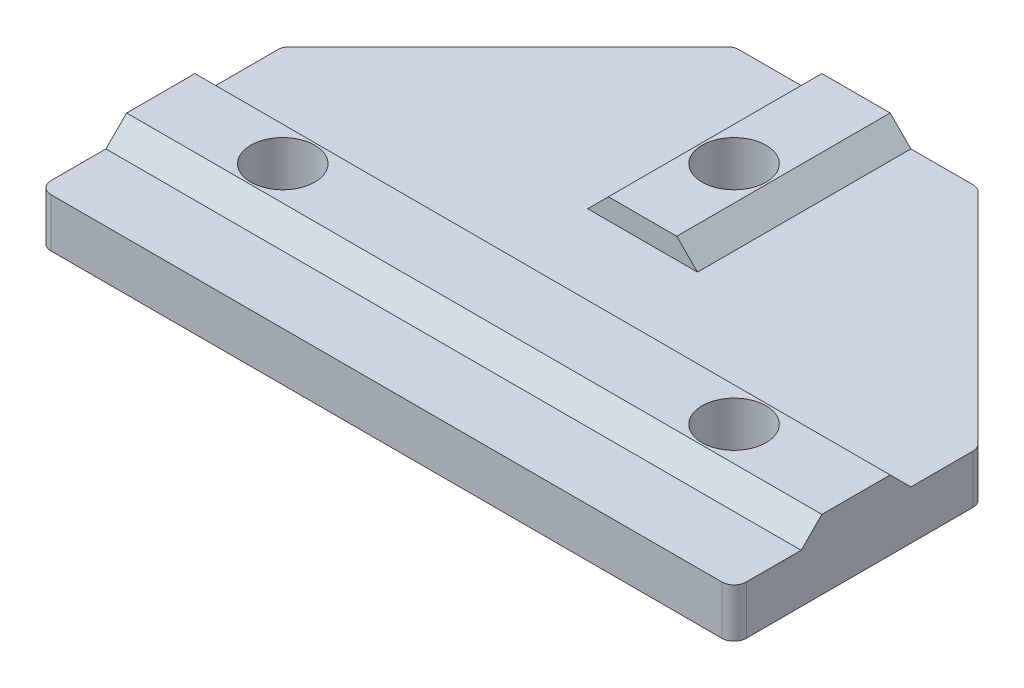
SolidWorks part; units mm, degrees
ref_plane "Front Plane" through (0, 0, 0) normal (0, 0, 1) x (1, 0, 0)
ref_plane "Top Plane" through (0, 0, 0) normal (0, 1, 0) x (1, 0, 0)
ref_plane "Right Plane" through (0, 0, 0) normal (1, 0, 0) x (0, 0, -1)
sketch "Sketch1" plane through (0, 0, 0) normal (0, 1, 0) x (1, 0, 0)
  line L0 (0, 0) -> (57, 0)
  line L1 (57, 0) -> (57, 20)
  line L2 (57, 20) -> (38.5, 38.5)
  line L3 (38.5, 38.5) -> (18.5, 38.5)
  line L4 (18.5, 38.5) -> (0, 20)
  line L5 (0, 20) -> (0, 0)
  dimension "D1" = 135
  dimension "D2" = 135
  dimension "D3" = 57
  dimension "D4" = 38.5
  dimension "D5" = 20
extrude "Boss-Extrude1" add sketch "Sketch1" along normal blind 4
sketch "Sketch2" plane through (0, 4, 0) normal (0, 1, 0) x (1, 0, 0)
  line L0 (38.5, 38.5) -> (18.5, 38.5) construction
  line L1 (33, 38.5) -> (24, 38.5)
  line L2 (33, 38.5) -> (33, 21)
  line L3 (33, 21) -> (24, 21)
  line L4 (24, 38.5) -> (24, 21)
  line L5 (0, 20) -> (0, 0) construction
  line L6 (0, 14.5) -> (57, 14.5)
  line L7 (0, 14.5) -> (0, 5.5)
  line L8 (0, 5.5) -> (57, 5.5)
  line L9 (57, 14.5) -> (57, 5.5)
  line L10 (57, 0) -> (57, 20) construction
  line L11 (0, 0) -> (57, 0) construction
  dimension "D1" = 9
  dimension "D2" = 9
  dimension "D3" = 24
  dimension "D4" = 5.5
  dimension "D5" = 17.5
extrude "Boss-Extrude2" add sketch "Sketch2" along normal blind 1.7
chamfer "Chamfer1" distance 1.7 angle 45 4 edges at (33, 5.7, -29.75) (28.5, 5.7, -14.5) (24, 5.7, -29.75) (28.5, 5.7, -5.5)
sketch "Sketch4" plane through (0, 0, 0) normal (0, -1, 0) x (1, 0, 0)
  line L1 (0, 0) -> (57, 0) construction
  line L2 (0, -20) -> (0, 0) construction
  line L3 (57, 0) -> (57, -20) construction
  line L4 (38.5, -38.5) -> (18.5, -38.5) construction
  circle A0 centre (10, -10) radius 2.625
  circle A1 centre (47, -10) radius 2.625
  circle A2 centre (28.5, -28.5) radius 2.625
  dimension "D1" = 5.25
  dimension "D2" = 5.25
  dimension "D3" = 5.25
  dimension "D4" = 10
  dimension "D5" = 10
  dimension "D6" = 10
  dimension "D8" = 28.5
  dimension "D9" = 10
  dimension "D7" = 10
extrude "Cut-Extrude1" cut sketch "Sketch4" against normal through all
fillet "Fillet1" radius 1 6 edges at (18.5, 2, -38.5) (0, 2, -20) (0, 2, 0) (57, 2, 0) (57, 2, -20) (38.5, 2, -38.5)
